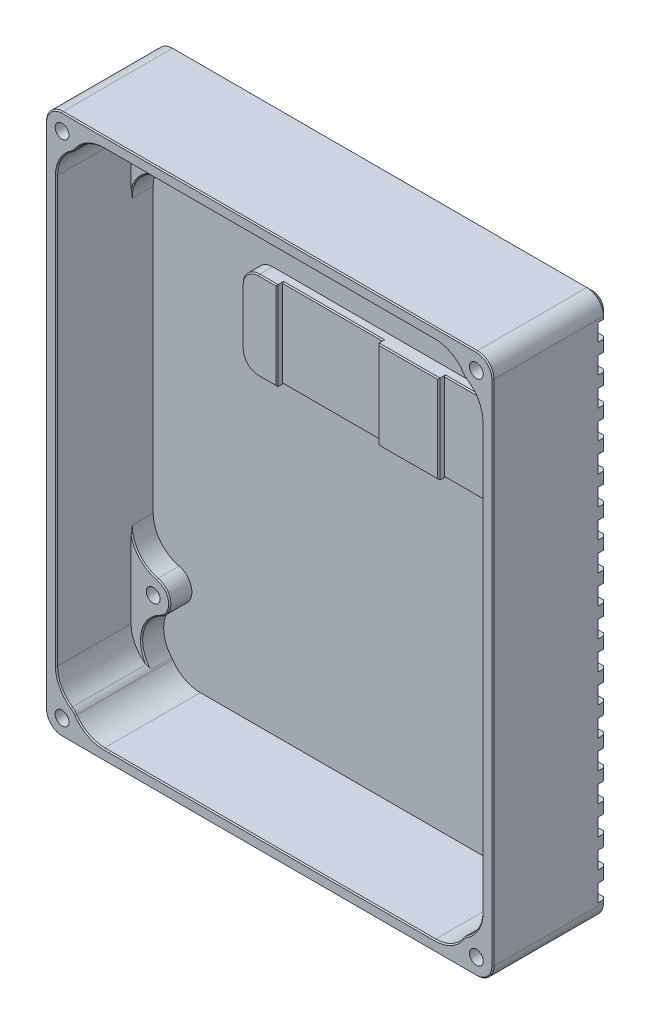
SolidWorks part; units mm, degrees
ref_plane "Front Plane" through (0, 0, 0) normal (0, 0, 1) x (1, 0, 0)
ref_plane "Top Plane" through (0, 0, 0) normal (0, 1, 0) x (1, 0, 0)
ref_plane "Right Plane" through (0, 0, 0) normal (1, 0, 0) x (0, 0, -1)
sketch "Sketch1" plane through (0, 0, 0) normal (0, 0, 1) x (1, 0, 0)
  line L0 (-38.5, 44.5) -> (-38.5, -49.5) construction
  line L1 (34.5, -34.5) -> (-34.5, -34.5) construction
  line L2 (34.5, -34.5) -> (34.5, 34.5) construction
  line L3 (34.5, 34.5) -> (-34.5, 34.5) construction
  line L4 (-34.5, -34.5) -> (-34.5, 34.5) construction
  line L5 (34.5, -34.5) -> (-34.5, 34.5) construction
  line L6 (34.5, 34.5) -> (-34.5, -34.5) construction
  line L7 (37.5, -37.5) -> (-37.5, -37.5) construction
  line L8 (37.5, -37.5) -> (37.5, 37.5) construction
  line L9 (37.5, 37.5) -> (-37.5, 37.5) construction
  line L10 (-37.5, -37.5) -> (-37.5, 37.5) construction
  line L11 (37.5, -37.5) -> (-37.5, 37.5) construction
  line L12 (37.5, 37.5) -> (-37.5, -37.5) construction
  line L13 (-38.5, -49.5) -> (38.5, -49.5) construction
  line L14 (38.5, -49.5) -> (38.5, 44.5) construction
  line L15 (38.5, 44.5) -> (-38.5, 44.5) construction
  line L16 (-40.5, -51.5) -> (40.5, -51.5)
  line L17 (40.5, -51.5) -> (40.5, 46.5)
  line L18 (40.5, 46.5) -> (-40.5, 46.5)
  line L19 (-40.5, 46.5) -> (-40.5, -51.5)
  line L21 (-40.5, -2.5) -> (40.5, -2.5) construction
  line L22 (0, -53.35) -> (0, 53.35) construction
  circle A0 centre (-34.5, 34.5) radius 1.55 construction
  circle A1 centre (34.5, 34.5) radius 1.55 construction
  circle A2 centre (-34.5, -34.5) radius 1.55 construction
  circle A3 centre (34.5, -34.5) radius 1.55 construction
  circle A4 centre (-37.5, 43.5) radius 3 construction
  arc A7 (-35.0154, 41.8187) -> (-29.9634, 44.5) centre (-29.9634, 38.4) cw construction
  arc A8 (-38.5, 35.9634) -> (-35.8187, 41.0154) centre (-32.4, 35.9634) cw construction
  arc A9 (38.5, 35.9634) -> (35.8187, 41.0154) centre (32.4, 35.9634) ccw construction
  circle A11 centre (37.5, 43.5) radius 3 construction
  arc A12 (35.0154, 41.8187) -> (29.9634, 44.5) centre (29.9634, 38.4) ccw construction
  arc A13 (-38.5, -40.9634) -> (-35.8187, -46.0154) centre (-32.4, -40.9634) ccw construction
  circle A15 centre (-37.5, -48.5) radius 3 construction
  arc A17 (-35.0154, -46.8187) -> (-29.9634, -49.5) centre (-29.9634, -43.4) ccw construction
  arc A18 (35.0154, -46.8187) -> (29.9634, -49.5) centre (29.9634, -43.4) cw construction
  circle A19 centre (37.5, -48.5) radius 3 construction
  arc A20 (38.5, -40.9634) -> (35.8187, -46.0154) centre (32.4, -40.9634) cw construction
  point P0 (0, 0)
  point P10 (0, 0)
  dimension "D2" = 3.1
  dimension "D9" = 6
  dimension "D10" = 6.1
  dimension "D1" = 69
  dimension "D3" = 75
  dimension "D4" = 1
  dimension "D5" = 1
  dimension "D6" = 12
  dimension "D7" = 7
  dimension "D8" = 2
extrude "Boss-Extrude1" add sketch "Sketch1" along normal mid plane 21
sketch "Sketch3" plane through (0, 0, 10.5) normal (0, 0, 1) x (1, 0, 0)
  line L0 (38.5, 44.5) -> (-38.5, 44.5) construction
  line L1 (29.9634, 44.5) -> (-29.9634, 44.5)
  line L2 (-38.5, 44.5) -> (-38.5, -49.5) construction
  line L3 (-38.5, 35.9634) -> (-38.5, -49.5)
  line L4 (-38.5, 44.5) -> (-38.5, 40.6716) construction
  line L5 (-34.6716, 44.5) -> (-38.5, 44.5) construction
  line L6 (-38.5, 40.6716) -> (-38.5, 35.9634) construction
  line L7 (-29.9634, 44.5) -> (-34.6716, 44.5) construction
  line L8 (38.5, 44.5) -> (34.6716, 44.5) construction
  line L9 (34.6716, 44.5) -> (29.9634, 44.5) construction
  line L10 (-38.5, -49.5) -> (38.5, -49.5) construction
  line L11 (38.5, -49.5) -> (38.5, 44.5) construction
  line L12 (-38.5, -49.5) -> (29.9634, -49.5)
  line L13 (38.5, -40.9634) -> (38.5, 44.5)
  line L14 (38.5, -49.5) -> (38.5, -45.6716) construction
  line L15 (34.6716, -49.5) -> (38.5, -49.5) construction
  line L16 (38.5, -45.6716) -> (38.5, -40.9634) construction
  line L17 (29.9634, -49.5) -> (34.6716, -49.5) construction
  arc A0 (38.5, 35.9634) -> (35.8187, 41.0154) centre (32.4, 35.9634) ccw construction
  circle A1 centre (37.5, 43.5) radius 3 construction
  arc A2 (35.0154, 41.8187) -> (29.9634, 44.5) centre (29.9634, 38.4) ccw construction
  arc A3 (29.9634, -49.5) -> (35.0154, -46.8187) centre (29.9634, -43.4) ccw construction
  circle A4 centre (37.5, -48.5) radius 3 construction
  arc A5 (35.8187, -46.0154) -> (38.5, -40.9634) centre (32.4, -40.9634) ccw construction
  arc A6 (-38.5, -40.9634) -> (-35.8187, -46.0154) centre (-32.4, -40.9634) ccw construction
  circle A7 centre (-37.5, -48.5) radius 3 construction
  arc A8 (-35.0154, -46.8187) -> (-29.9634, -49.5) centre (-29.9634, -43.4) ccw construction
  arc A9 (-35.8187, 41.0154) -> (-38.5, 35.9634) centre (-32.4, 35.9634) ccw construction
  circle A10 centre (-37.5, 43.5) radius 3 construction
  arc A11 (-29.9634, 44.5) -> (-35.0154, 41.8187) centre (-29.9634, 38.4) ccw construction
  arc A12 (38.5, 35.9634) -> (35.8187, 41.0154) centre (32.4, 35.9634) ccw
  arc A13 (35.0154, 41.8187) -> (35.8187, 41.0154) centre (37.5, 43.5) ccw
  arc A14 (35.0154, 41.8187) -> (29.9634, 44.5) centre (29.9634, 38.4) ccw
  arc A15 (29.9634, -49.5) -> (35.0154, -46.8187) centre (29.9634, -43.4) ccw
  arc A16 (35.8187, -46.0154) -> (35.0154, -46.8187) centre (37.5, -48.5) ccw
  arc A17 (35.8187, -46.0154) -> (38.5, -40.9634) centre (32.4, -40.9634) ccw
  arc A18 (-38.5, -40.9634) -> (-35.8187, -46.0154) centre (-32.4, -40.9634) ccw
  circle A19 centre (-37.5, -48.5) radius 3
  arc A20 (-35.0154, -46.8187) -> (-29.9634, -49.5) centre (-29.9634, -43.4) ccw
  arc A21 (-35.8187, 41.0154) -> (-38.5, 35.9634) centre (-32.4, 35.9634) ccw
  arc A22 (-35.8187, 41.0154) -> (-35.0154, 41.8187) centre (-37.5, 43.5) ccw
  arc A23 (-29.9634, 44.5) -> (-35.0154, 41.8187) centre (-29.9634, 38.4) ccw
  arc A24 (-35.0154, 41.8187) -> (-34.6716, 44.5) centre (-37.5, 43.5) ccw construction
  arc A25 (-34.6716, 44.5) -> (-38.5, 40.6716) centre (-37.5, 43.5) ccw construction
  arc A26 (-38.5, 40.6716) -> (-35.8187, 41.0154) centre (-37.5, 43.5) ccw construction
  arc A27 (35.8187, 41.0154) -> (34.6716, 44.5) centre (37.5, 43.5) ccw construction
  arc A28 (34.6716, 44.5) -> (35.0154, 41.8187) centre (37.5, 43.5) ccw construction
  arc A29 (34.6716, -49.5) -> (38.5, -45.6716) centre (37.5, -48.5) ccw construction
  arc A30 (35.0154, -46.8187) -> (34.6716, -49.5) centre (37.5, -48.5) ccw construction
  arc A31 (38.5, -45.6716) -> (35.8187, -46.0154) centre (37.5, -48.5) ccw construction
extrude "Cut-Extrude1" cut sketch "Sketch3" against normal offset from surface (17.5 mm away) 3.5 contours L1 A23 A22 A21 L3 A18 A19 A20 L12 A15 A16 A17 L13 A12 A13 A14 up to face at (0, -2.5, -10.5)
sketch "Sketch4" plane through (0, 0, -7) normal (0, 0, 1) x (1, 0, 0)
  line L0 (-38.5, 44.5) -> (-38.5, -49.5) construction
  line L4 (0, -53.35) -> (0, 53.35) construction
  line L8 (29.9634, 44.5) -> (-29.9634, 44.5)
  line L9 (-38.5, 35.9634) -> (-38.5, -40.9634)
  line L10 (-29.9634, -49.5) -> (29.9634, -49.5)
  line L11 (38.5, -40.9634) -> (38.5, 35.9634)
  line L12 (29.9634, 44.5) -> (-29.9634, 44.5)
  line L13 (-38.5, 35.9634) -> (-38.5, -40.9634)
  line L14 (-29.9634, -49.5) -> (29.9634, -49.5)
  line L15 (38.5, -40.9634) -> (38.5, 35.9634)
  arc A0 (-33.8077, 31.581) -> (-31.7895, 35.7857) centre (-34.5, 34.5) ccw
  arc A1 (-33.8077, 31.581) -> (-38.5, 25.6456) centre (-32.4, 25.6456) ccw
  arc A3 (-26.2781, 44.5) -> (-31.7895, 35.7857) centre (-26.2781, 38.4) ccw
  arc A4 (-31.7895, 35.7857) -> (-33.8077, 31.581) centre (-34.5, 34.5) ccw construction
  arc A5 (33.8077, 31.581) -> (38.5, 25.6456) centre (32.4, 25.6456) cw
  arc A6 (33.8077, 31.581) -> (31.7895, 35.7857) centre (34.5, 34.5) cw
  arc A7 (26.2781, 44.5) -> (31.7895, 35.7857) centre (26.2781, 38.4) cw
  arc A8 (-33.1836, -37.1957) -> (-33.8077, -31.581) centre (-34.5, -34.5) ccw
  arc A9 (33.8077, -31.581) -> (33.1836, -37.1957) centre (34.5, -34.5) ccw
  arc A10 (-38.5, -25.6456) -> (-33.8077, -31.581) centre (-32.4, -25.6456) ccw
  arc A11 (-33.1836, -37.1957) -> (-35.1946, -46.5804) centre (-30.5069, -42.6771) ccw
  arc A12 (33.1836, -37.1957) -> (35.1946, -46.5804) centre (30.5069, -42.6771) cw
  arc A13 (33.1836, -37.1957) -> (33.8077, -31.581) centre (34.5, -34.5) cw
  arc A14 (38.5, -25.6456) -> (33.8077, -31.581) centre (32.4, -25.6456) cw
  arc A15 (-29.9634, 44.5) -> (-35.0154, 41.8187) centre (-29.9634, 38.4) ccw
  arc A16 (-35.8187, 41.0154) -> (-35.0154, 41.8187) centre (-37.5, 43.5) ccw
  arc A17 (-35.8187, 41.0154) -> (-38.5, 35.9634) centre (-32.4, 35.9634) ccw
  arc A18 (-38.5, -40.9634) -> (-35.8187, -46.0154) centre (-32.4, -40.9634) ccw
  arc A19 (-35.0154, -46.8187) -> (-35.8187, -46.0154) centre (-37.5, -48.5) ccw
  arc A20 (-35.0154, -46.8187) -> (-29.9634, -49.5) centre (-29.9634, -43.4) ccw
  arc A21 (29.9634, -49.5) -> (35.0154, -46.8187) centre (29.9634, -43.4) ccw
  arc A22 (35.8187, -46.0154) -> (35.0154, -46.8187) centre (37.5, -48.5) ccw
  arc A23 (35.8187, -46.0154) -> (38.5, -40.9634) centre (32.4, -40.9634) ccw
  arc A24 (38.5, 35.9634) -> (35.8187, 41.0154) centre (32.4, 35.9634) ccw
  arc A25 (35.0154, 41.8187) -> (35.8187, 41.0154) centre (37.5, 43.5) ccw
  arc A26 (35.0154, 41.8187) -> (29.9634, 44.5) centre (29.9634, 38.4) ccw
  arc A27 (-29.9634, 44.5) -> (-35.0154, 41.8187) centre (-29.9634, 38.4) ccw
  arc A28 (-35.8187, 41.0154) -> (-35.0154, 41.8187) centre (-37.5, 43.5) ccw
  arc A29 (-35.8187, 41.0154) -> (-38.5, 35.9634) centre (-32.4, 35.9634) ccw
  arc A30 (-38.5, -40.9634) -> (-35.8187, -46.0154) centre (-32.4, -40.9634) ccw
  arc A31 (-35.0154, -46.8187) -> (-35.8187, -46.0154) centre (-37.5, -48.5) ccw
  arc A32 (-35.0154, -46.8187) -> (-29.9634, -49.5) centre (-29.9634, -43.4) ccw
  arc A33 (29.9634, -49.5) -> (35.0154, -46.8187) centre (29.9634, -43.4) ccw
  arc A34 (35.8187, -46.0154) -> (35.0154, -46.8187) centre (37.5, -48.5) ccw
  arc A35 (35.8187, -46.0154) -> (38.5, -40.9634) centre (32.4, -40.9634) ccw
  arc A36 (38.5, 35.9634) -> (35.8187, 41.0154) centre (32.4, 35.9634) ccw
  arc A37 (35.0154, 41.8187) -> (35.8187, 41.0154) centre (37.5, 43.5) ccw
  arc A38 (35.0154, 41.8187) -> (29.9634, 44.5) centre (29.9634, 38.4) ccw
  point P41 (34.5, -34.5)
  point P46 (-34.5, -34.5)
  line M17 (29.9634, 44.5) -> (-29.9634, 44.5)
  arc M18 (-29.9634, 44.5) -> (-35.0154, 41.8187) centre (-29.9634, 38.4) ccw
  arc M19 (-35.0154, 41.8187) -> (-35.8187, 41.0154) centre (-37.5, 43.5) cw
  arc M20 (-35.8187, 41.0154) -> (-38.5, 35.9634) centre (-32.4, 35.9634) ccw
  line M21 (-38.5, 35.9634) -> (-38.5, -40.9634)
  arc M22 (-38.5, -40.9634) -> (-35.8187, -46.0154) centre (-32.4, -40.9634) ccw
  arc M23 (-35.8187, -46.0154) -> (-35.0154, -46.8187) centre (-37.5, -48.5) cw
  arc M27 (35.0154, -46.8187) -> (35.8187, -46.0154) centre (37.5, -48.5) cw
  arc M28 (35.8187, -46.0154) -> (38.5, -40.9634) centre (32.4, -40.9634) ccw
  line M29 (38.5, -40.9634) -> (38.5, 35.9634)
  arc M30 (38.5, 35.9634) -> (35.8187, 41.0154) centre (32.4, 35.9634) ccw
  arc M31 (35.8187, 41.0154) -> (35.0154, 41.8187) centre (37.5, 43.5) cw
  arc M32 (35.0154, 41.8187) -> (29.9634, 44.5) centre (29.9634, 38.4) ccw
  dimension "D1" = 6
  dimension "D2" = 12.2
  dimension "D3" = 0
extrude "Boss-Extrude2" add sketch "Sketch4" along normal blind 4 contours A3 L12 A1 A0 M18 M19 M20 M21 | A7 A6 A5 L15 M17 M30 M31 M32 | A11 A8 A10 M21 M22 M23 | A14 A9 A12 M29 M27 M28
sketch "Sketch5" plane through (0, 0, -7) normal (0, 0, 1) x (1, 0, 0)
  line L0 (38.5, -49.5) -> (38.5, 44.5) construction
  line L1 (38.5, 23.8) -> (34.5, 23.8) construction
  line L2 (38.5, 23.8) -> (38.5, 7.8)
  line L3 (32.4, 7.8) -> (-19.9, 7.8)
  line L4 (-19.9, 23.8) -> (-19.9, 7.8)
  line L7 (37.5, 37.5) -> (-37.5, 37.5) construction
  line L8 (37.5, -37.5) -> (37.5, 37.5) construction
  line L9 (34.5, -34.5) -> (34.5, 34.5) construction
  line L10 (34.5, -34.5) -> (34.5, 34.5) construction
  line L11 (26.6482, 23.8) -> (-19.9, 23.8)
  line L12 (34.5, 23.8) -> (26.6482, 23.8) construction
  line L13 (38.5, -25.6456) -> (38.5, 25.6456)
  line L14 (26.2781, 44.5) -> (-26.2781, 44.5)
  line L15 (-38.5, 25.6456) -> (-38.5, -25.6456)
  line L16 (-29.9634, -49.5) -> (29.9634, -49.5)
  line L17 (38.5, -25.6456) -> (38.5, 25.6456)
  line L18 (26.2781, 44.5) -> (-26.2781, 44.5)
  line L19 (-38.5, 25.6456) -> (-38.5, -25.6456)
  line L20 (-29.9634, -49.5) -> (29.9634, -49.5)
  line L21 (38.5, 7.8) -> (34.5, 7.8) construction
  line L22 (34.5, 7.8) -> (32.4, 7.8) construction
  line L23 (16.2, 23.8) -> (16.2, 7.8) construction
  line L24 (33.5, 23.8) -> (33.5, 7.8) construction
  line L26 (14.5, 10) -> (9.9, 10) construction
  line L27 (14.5, 10) -> (14.5, 15.6) construction
  line L28 (14.5, 15.6) -> (9.9, 15.6) construction
  line L29 (9.9, 10) -> (9.9, 15.6) construction
  line L30 (14.5, 10) -> (9.9, 15.6) construction
  line L31 (14.5, 15.6) -> (9.9, 10) construction
  line L32 (4.2, 23.8) -> (4.2, 7.8) construction
  line L33 (-13.1, 23.8) -> (-13.1, 7.8) construction
  line L35 (-14.8, 10) -> (-19.4, 10) construction
  line L36 (-14.8, 10) -> (-14.8, 15.6) construction
  line L37 (-14.8, 15.6) -> (-19.4, 15.6) construction
  line L38 (-19.4, 10) -> (-19.4, 15.6) construction
  line L39 (-14.8, 10) -> (-19.4, 15.6) construction
  line L40 (-14.8, 15.6) -> (-19.4, 10) construction
  arc A0 (26.6482, 23.8) -> (31.9115, 32.9835) centre (26.6482, 29.9) ccw
  arc A1 (31.7895, 35.7857) -> (33.8077, 31.581) centre (34.5, 34.5) ccw construction
  arc A2 (38.5, 1.7) -> (32.4, 7.8) centre (32.4, 1.7) ccw
  arc A18 (33.8077, -31.581) -> (33.1836, -37.1957) centre (34.5, -34.5) ccw
  arc A19 (33.8077, -31.581) -> (38.5, -25.6456) centre (32.4, -25.6456) ccw
  arc A20 (38.5, 25.6456) -> (33.8077, 31.581) centre (32.4, 25.6456) ccw
  arc A21 (31.7895, 35.7857) -> (33.8077, 31.581) centre (34.5, 34.5) ccw
  arc A22 (31.7895, 35.7857) -> (26.2781, 44.5) centre (26.2781, 38.4) ccw
  arc A23 (-26.2781, 44.5) -> (-31.7895, 35.7857) centre (-26.2781, 38.4) ccw
  arc A24 (-33.8077, 31.581) -> (-31.7895, 35.7857) centre (-34.5, 34.5) ccw
  arc A25 (-33.8077, 31.581) -> (-38.5, 25.6456) centre (-32.4, 25.6456) ccw
  arc A26 (-38.5, -25.6456) -> (-33.8077, -31.581) centre (-32.4, -25.6456) ccw
  arc A27 (-33.1836, -37.1957) -> (-33.8077, -31.581) centre (-34.5, -34.5) ccw
  arc A28 (-33.1836, -37.1957) -> (-35.1946, -46.5804) centre (-30.5069, -42.6771) ccw
  arc A29 (-35.0154, -46.8187) -> (-35.1946, -46.5804) centre (-37.5, -48.5) ccw
  arc A30 (-35.0154, -46.8187) -> (-29.9634, -49.5) centre (-29.9634, -43.4) ccw
  arc A31 (29.9634, -49.5) -> (35.0154, -46.8187) centre (29.9634, -43.4) ccw
  arc A32 (35.1946, -46.5804) -> (35.0154, -46.8187) centre (37.5, -48.5) ccw
  arc A33 (35.1946, -46.5804) -> (33.1836, -37.1957) centre (30.5069, -42.6771) ccw
  arc A34 (33.8077, -31.581) -> (33.1836, -37.1957) centre (34.5, -34.5) ccw
  arc A35 (33.8077, -31.581) -> (38.5, -25.6456) centre (32.4, -25.6456) ccw
  arc A36 (38.5, 25.6456) -> (33.8077, 31.581) centre (32.4, 25.6456) ccw
  arc A37 (31.7895, 35.7857) -> (33.8077, 31.581) centre (34.5, 34.5) ccw
  arc A38 (31.7895, 35.7857) -> (26.2781, 44.5) centre (26.2781, 38.4) ccw
  arc A39 (-26.2781, 44.5) -> (-31.7895, 35.7857) centre (-26.2781, 38.4) ccw
  arc A40 (-33.8077, 31.581) -> (-31.7895, 35.7857) centre (-34.5, 34.5) ccw
  arc A41 (-33.8077, 31.581) -> (-38.5, 25.6456) centre (-32.4, 25.6456) ccw
  arc A42 (-38.5, -25.6456) -> (-33.8077, -31.581) centre (-32.4, -25.6456) ccw
  arc A43 (-33.1836, -37.1957) -> (-33.8077, -31.581) centre (-34.5, -34.5) ccw
  arc A44 (-33.1836, -37.1957) -> (-35.1946, -46.5804) centre (-30.5069, -42.6771) ccw
  arc A45 (-35.0154, -46.8187) -> (-35.1946, -46.5804) centre (-37.5, -48.5) ccw
  arc A46 (-35.0154, -46.8187) -> (-29.9634, -49.5) centre (-29.9634, -43.4) ccw
  arc A47 (29.9634, -49.5) -> (35.0154, -46.8187) centre (29.9634, -43.4) ccw
  arc A48 (35.1946, -46.5804) -> (35.0154, -46.8187) centre (37.5, -48.5) ccw
  arc A49 (35.1946, -46.5804) -> (33.1836, -37.1957) centre (30.5069, -42.6771) ccw
  point P56 (12.2, 12.8)
  point P75 (-17.1, 12.8)
  line M27 (38.5, -25.6456) -> (38.5, 25.6456)
  arc M28 (38.5, 25.6456) -> (33.8077, 31.581) centre (32.4, 25.6456) ccw
  arc M29 (33.8077, 31.581) -> (31.7895, 35.7857) centre (34.5, 34.5) cw
  dimension "D4" = 12.2
  dimension "D1" = 13.7
  dimension "D2" = 16
  dimension "D3" = 0.5
  dimension "D6" = 17.3
  dimension "D7" = 4
  dimension "D8" = 1.7
  dimension "D9" = 4.6
  dimension "D10" = 5.6
  dimension "D11" = 5.7
  dimension "D12" = 17.3
  dimension "D13" = 27.5
  dimension "D14" = 1.7
  dimension "D5" = 0
extrude "Boss-Extrude3" add sketch "Sketch5" along normal blind 1.5 contours A2 L17 A0 L11 L4 L3 M27 M28 M29
sketch "Sketch7" plane through (0, 0, -5.5) normal (0, 0, 1) x (1, 0, 0)
  line L2 (-13.6, 23.8) -> (-13.6, 7.8)
  line L3 (-13.6, 23.8) -> (-13.6, 7.8)
  line L5 (4.7, 23.8) -> (4.7, 7.8)
  line L6 (4.7, 23.8) -> (4.7, 7.8)
  line L8 (32.4, 7.8) -> (-19.9, 7.8) construction
  line L9 (15.7, 23.8) -> (15.7, 7.8)
  line L10 (15.7, 23.8) -> (15.7, 7.8)
  line L11 (-19.9, 23.8) -> (-19.9, 7.8) construction
  line L12 (26.6482, 23.8) -> (-19.9, 23.8) construction
  line L13 (32.4, 7.8) -> (-19.9, 7.8)
  line L14 (-19.9, 23.8) -> (-19.9, 7.8)
  line L15 (26.6482, 23.8) -> (-19.9, 23.8)
  line M9 (26.6482, 23.8) -> (-19.9, 23.8)
  line M10 (-19.9, 23.8) -> (-19.9, 7.8)
  line M11 (-19.9, 7.8) -> (32.4, 7.8)
  dimension "D1" = 0.5
  dimension "D2" = 0.5
  dimension "D3" = 0.5
extrude "Boss-Extrude4" add sketch "Sketch7" along normal blind 1 contours L3 M9 M10 M11 | L10 L6 M9 M11
fillet "Fillet1" radius 3 4 edges at (-40.5, -51.5, 0) (40.5, -51.5, 0) (40.5, 46.5, 0) (-40.5, 46.5, 0)
chamfer "Chamfer1" distance 1 angle 45 8 edges at (40.5, -2.5, -10.5) (39.6213, 45.6213, -10.5) (39.6213, -50.6213, -10.5) (0, 46.5, -10.5) (0, -51.5, -10.5) (-39.6213, 45.6213, -10.5) (-39.6213, -50.6213, -10.5) (-40.5, -2.5, -10.5)
sketch "Sketch8" plane through (0, 0, -10.5) normal (0, 0, -1) x (-1, 0, 0)
  line L0 (-37.5, 46.5) -> (37.5, 46.5) construction
  line L1 (-53.8814, 39.9) -> (53.8814, 39.9)
  line L2 (-53.8814, 39.9) -> (-53.8814, 43)
  line L3 (-53.8814, 43) -> (53.8814, 43)
  line L4 (53.8814, 39.9) -> (53.8814, 43)
  line L5 (-53.8814, 39.9) -> (53.8814, 43) construction
  line L6 (-53.8814, 43) -> (53.8814, 39.9) construction
  line L7 (-53.8814, 37.8294) -> (53.8814, 37.8294)
  line L8 (-53.8814, 34.7294) -> (-53.8814, 37.8294)
  line L9 (-53.8814, 34.7294) -> (53.8814, 34.7294)
  line L10 (53.8814, 34.7294) -> (53.8814, 37.8294)
  line L11 (-53.8814, 32.6588) -> (53.8814, 32.6588)
  line L12 (-53.8814, 29.5588) -> (-53.8814, 32.6588)
  line L13 (-53.8814, 29.5588) -> (53.8814, 29.5588)
  line L14 (53.8814, 29.5588) -> (53.8814, 32.6588)
  line L15 (-53.8814, 27.4882) -> (53.8814, 27.4882)
  line L16 (-53.8814, 24.3882) -> (-53.8814, 27.4882)
  line L17 (-53.8814, 24.3882) -> (53.8814, 24.3882)
  line L18 (53.8814, 24.3882) -> (53.8814, 27.4882)
  line L19 (-53.8814, 22.3176) -> (53.8814, 22.3176)
  line L20 (-53.8814, 19.2176) -> (-53.8814, 22.3176)
  line L21 (-53.8814, 19.2176) -> (53.8814, 19.2176)
  line L22 (53.8814, 19.2176) -> (53.8814, 22.3176)
  line L23 (-53.8814, 17.1471) -> (53.8814, 17.1471)
  line L24 (-53.8814, 14.0471) -> (-53.8814, 17.1471)
  line L25 (-53.8814, 14.0471) -> (53.8814, 14.0471)
  line L26 (53.8814, 14.0471) -> (53.8814, 17.1471)
  line L27 (-53.8814, 11.9765) -> (53.8814, 11.9765)
  line L28 (-53.8814, 8.8765) -> (-53.8814, 11.9765)
  line L29 (-53.8814, 8.8765) -> (53.8814, 8.8765)
  line L30 (53.8814, 8.8765) -> (53.8814, 11.9765)
  line L31 (-53.8814, 6.8059) -> (53.8814, 6.8059)
  line L32 (-53.8814, 3.7059) -> (-53.8814, 6.8059)
  line L33 (-53.8814, 3.7059) -> (53.8814, 3.7059)
  line L34 (53.8814, 3.7059) -> (53.8814, 6.8059)
  line L35 (-53.8814, 1.6353) -> (53.8814, 1.6353)
  line L36 (-53.8814, -1.4647) -> (-53.8814, 1.6353)
  line L37 (-53.8814, -1.4647) -> (53.8814, -1.4647)
  line L38 (53.8814, -1.4647) -> (53.8814, 1.6353)
  line L39 (-53.8814, -3.5353) -> (53.8814, -3.5353)
  line L40 (-53.8814, -6.6353) -> (-53.8814, -3.5353)
  line L41 (-53.8814, -6.6353) -> (53.8814, -6.6353)
  line L42 (53.8814, -6.6353) -> (53.8814, -3.5353)
  line L43 (-53.8814, -8.7059) -> (53.8814, -8.7059)
  line L44 (-53.8814, -11.8059) -> (-53.8814, -8.7059)
  line L45 (-53.8814, -11.8059) -> (53.8814, -11.8059)
  line L46 (53.8814, -11.8059) -> (53.8814, -8.7059)
  line L47 (-53.8814, -13.8765) -> (53.8814, -13.8765)
  line L48 (-53.8814, -16.9765) -> (-53.8814, -13.8765)
  line L49 (-53.8814, -16.9765) -> (53.8814, -16.9765)
  line L50 (53.8814, -16.9765) -> (53.8814, -13.8765)
  line L51 (-53.8814, -19.0471) -> (53.8814, -19.0471)
  line L52 (-53.8814, -22.1471) -> (-53.8814, -19.0471)
  line L53 (-53.8814, -22.1471) -> (53.8814, -22.1471)
  line L54 (53.8814, -22.1471) -> (53.8814, -19.0471)
  line L55 (-53.8814, -24.2176) -> (53.8814, -24.2176)
  line L56 (-53.8814, -27.3176) -> (-53.8814, -24.2176)
  line L57 (-53.8814, -27.3176) -> (53.8814, -27.3176)
  line L58 (53.8814, -27.3176) -> (53.8814, -24.2176)
  line L59 (-53.8814, -29.3882) -> (53.8814, -29.3882)
  line L60 (-53.8814, -32.4882) -> (-53.8814, -29.3882)
  line L61 (-53.8814, -32.4882) -> (53.8814, -32.4882)
  line L62 (53.8814, -32.4882) -> (53.8814, -29.3882)
  line L63 (-53.8814, -34.5588) -> (53.8814, -34.5588)
  line L64 (-53.8814, -37.6588) -> (-53.8814, -34.5588)
  line L65 (-53.8814, -37.6588) -> (53.8814, -37.6588)
  line L66 (53.8814, -37.6588) -> (53.8814, -34.5588)
  line L67 (-53.8814, -39.7294) -> (53.8814, -39.7294)
  line L68 (-53.8814, -42.8294) -> (-53.8814, -39.7294)
  line L69 (-53.8814, -42.8294) -> (53.8814, -42.8294)
  line L70 (53.8814, -42.8294) -> (53.8814, -39.7294)
  line L71 (-53.8814, -44.9) -> (53.8814, -44.9)
  line L72 (-53.8814, -48) -> (-53.8814, -44.9)
  line L73 (-53.8814, -48) -> (53.8814, -48)
  line L74 (53.8814, -48) -> (53.8814, -44.9)
  line L75 (37.5, -51.5) -> (-37.5, -51.5) construction
  point P0 (0, 41.45)
  dimension "D1" = 3.5
  dimension "D2" = 3.1
  dimension "D4" = 3.5
  dimension "D3" = 18
extrude "Cut-Extrude2" cut sketch "Sketch8" against normal blind 2
chamfer "Chamfer2" distance 0.5 angle 45 36 edges at (0, 43, -10.5) (0, 39.9, -10.5) (0, 37.8294, -10.5) (0, 34.7294, -10.5) (0, 32.6588, -10.5) (0, 29.5588, -10.5) (0, 27.4882, -10.5) (0, 24.3882, -10.5) (0, 22.3176, -10.5) (0, 19.2176, -10.5) (0, 17.1471, -10.5) (0, 14.0471, -10.5) (0, 11.9765, -10.5) (0, 8.8765, -10.5) (0, 6.8059, -10.5) (0, 3.7059, -10.5) (0, 1.6353, -10.5) (0, -1.4647, -10.5) (0, -3.5353, -10.5) (0, -6.6353, -10.5) (0, -8.7059, -10.5) (0, -11.8059, -10.5) (0, -13.8765, -10.5) (0, -16.9765, -10.5) (0, -19.0471, -10.5) (0, -22.1471, -10.5) (0, -24.2176, -10.5) (0, -27.3176, -10.5) (0, -29.3882, -10.5) (0, -32.4882, -10.5) (0, -34.5588, -10.5) (0, -37.6588, -10.5) (0, -39.7294, -10.5) (0, -42.8294, -10.5) (0, -44.9, -10.5) (0, -48, -10.5)
fillet "Fillet2" radius 3 2 edges at (-19.9, 23.8, -5.75) (-19.9, 7.8, -5.75)
chamfer "Chamfer3" distance 0.2 angle 45 54 edges at (-36.4715, -41.399, -3) (-37.1852, -29.4287, -3) (-31.5184, -34.1686, -3) (-35.4867, -46.2759, -3) (37.1852, -29.4287, -3) (31.5184, -34.1686, -3) (36.4715, -41.399, -3) (35.4867, -46.2759, -3) (36.7134, 6.0134, -5.5) (31.9407, 26.8668, -5.5) (24.05, 7.8, -5.5) (21.1741, 23.8, -5.5) (-13.6, 15.8, -4.5) (-15.25, 23.8, -4.5) (-4.45, 7.8, -5.5) (-4.45, 23.8, -5.5) (15.7, 15.8, -4.5) (10.2, 23.8, -4.5) (4.7, 15.8, -4.5) (10.2, 7.8, -4.5) (0, -51.5, 10.5) (-40.5, -2.5, 10.5) (40.5, -2.5, 10.5) (0, 46.5, 10.5) (-39.6213, 45.6213, 10.5) (39.6213, 45.6213, 10.5) (39.6213, -50.6213, 10.5) (-39.6213, -50.6213, 10.5) (35.3787, 41.3787, 10.5) (35.3787, -46.3787, 10.5) (-35.3787, -46.3787, 10.5) (-35.3787, 41.3787, 10.5) (0, 44.5, 10.5) (-32.8231, 43.7881, 10.5) (-37.7881, 38.8231, 10.5) (-38.5, -2.5, 10.5) (-37.7881, -43.8231, 10.5) (-32.8231, -48.7881, 10.5) (0, -49.5, 10.5) (32.8231, -48.7881, 10.5) (37.7881, -43.8231, 10.5) (38.5, -2.5, 10.5) (37.7881, 38.8231, 10.5) (32.8231, 43.7881, 10.5) (-31.4335, 41.6606, -3) (-37.1852, 29.4287, -3) (-31.7954, 33.2018, -3) (31.7954, 33.2018, -3) (31.4335, 41.6606, -3) (37.1852, 29.4287, -3) (-19.9, 15.8, -4.5) (-15.25, 7.8, -4.5) (-19.0213, 8.6787, -4.5) (-19.0213, 22.9213, -4.5)
sketch "Sketch10" plane through (0, 0, 10.5) normal (0, 0, 1) x (1, 0, 0)
  point P0 (37.5, -48.5)
  point P2 (37.5, 43.5)
  point P4 (-37.5, 43.5)
  point P6 (-37.5, -48.5)
hole_wizard "M3x0.5 Tapped Hole1" positions "3DSketch4" profile "Sketch11" tap size "M3x0.5" standard "ANSI Metric"
sketch3d "3DSketch4"
  point P0 (-37.5, 43.5, 10.5)
  point P3 (37.5, 43.5, 10.5)
  point P6 (-37.5, -48.5, 10.5)
  point P9 (37.5, -48.5, 10.5)
sketch "Sketch11" plane through (-37.5, 43.5, 10.5) normal (1, 0, 0) x (0, -1, 0)
  line L0 (0, 0) -> (0, 7.7511)
  line L1 (0, 7.7511) -> (1.25, 7)
  line L2 (1.25, 7) -> (1.25, 0)
  line L5 (1.25, 0) -> (0, 0)
  line L10 (0, 7.7511) -> (-1.25, 7) construction
  line L11 (0, -6.35) -> (0, 107.95) construction
  dimension "Tap Drill Dia." = 2.5
  dimension "Tap Drill Depth" = 7
  dimension "Drill Angle" = 118
cosmetic thread "Hole Thread1" parameters "D1"=6, "D2"=3
cosmetic thread "Hole Thread2" parameters "D1"=6, "D2"=3
cosmetic thread "Hole Thread3" parameters "D1"=6, "D2"=3
cosmetic thread "Hole Thread4" parameters "D1"=6, "D2"=3
hole_wizard "M3x0.5 Tapped Hole2" positions "3DSketch5" profile "Sketch12" tap size "M3x0.5" standard "ANSI Metric"
sketch3d "3DSketch5"
  line L0 (-34.5, 34.5, -3.2) -> (-34.5, 34.5, -3) construction
  line L1 (34.5, 34.5, -3.2) -> (34.5, 34.5, -3) construction
  line L2 (34.5, -34.5, -3.2) -> (34.5, -34.5, -3) construction
  line L3 (-34.5, -34.5, -3.2) -> (-34.5, -34.5, -3) construction
  point P0 (-34.5, 34.5, -3)
  point P4 (34.5, 34.5, -3)
  point P8 (34.5, -34.5, -3)
  point P12 (-34.5, -34.5, -3)
sketch "Sketch12" plane through (-34.5, 34.5, -3) normal (1, 0, 0) x (0, -1, 0)
  line L0 (0, 0) -> (0, 4.7511)
  line L1 (0, 4.7511) -> (1.25, 4)
  line L2 (1.25, 4) -> (1.25, 0)
  line L5 (1.25, 0) -> (0, 0)
  line L10 (0, 4.7511) -> (-1.25, 4) construction
  line L11 (0, -6.35) -> (0, 107.95) construction
  dimension "Tap Drill Dia." = 2.5
  dimension "Tap Drill Depth" = 4
  dimension "Drill Angle" = 118
cosmetic thread "Hole Thread5" parameters "D1"=4, "D2"=3
cosmetic thread "Hole Thread6" parameters "D1"=4, "D2"=3
cosmetic thread "Hole Thread7" parameters "D1"=4, "D2"=3
cosmetic thread "Hole Thread8" parameters "D1"=4, "D2"=3
